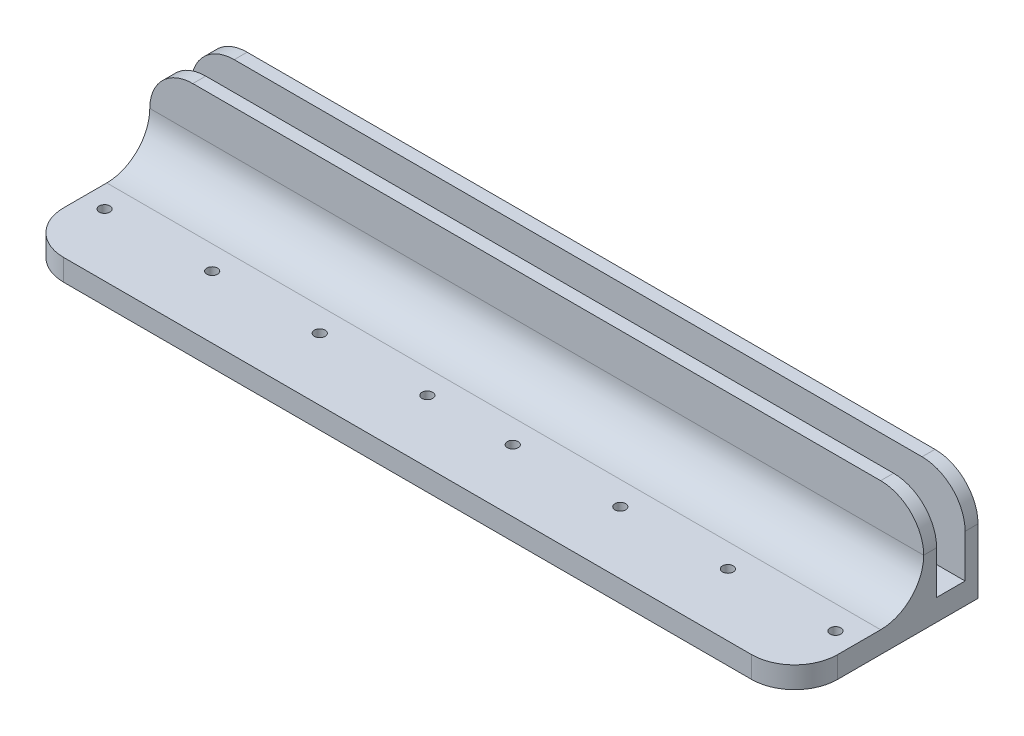
SolidWorks part; units mm, degrees
ref_plane "Front Plane" through (0, 0, 0) normal (0, 0, 1) x (1, 0, 0)
ref_plane "Top Plane" through (0, 0, 0) normal (0, 1, 0) x (1, 0, 0)
ref_plane "Right Plane" through (0, 0, 0) normal (1, 0, 0) x (0, 0, -1)
sketch "Sketch1" plane through (0, 0, 0) normal (0, 1, 0) x (1, 0, 0)
  line L1 (-80.9111, 25.148) -> (98.9289, 25.148)
  line L2 (-80.9111, 25.148) -> (-80.9111, -7.472)
  line L3 (-70.9111, -17.472) -> (88.9289, -17.472)
  line L4 (98.9289, 25.148) -> (98.9289, -7.472)
  line L5 (-80.9111, 25.148) -> (98.9289, 25.148)
  line L6 (-80.9111, 25.148) -> (-80.9111, 22.148)
  line L7 (-80.9111, 22.148) -> (98.9289, 22.148)
  line L8 (98.9289, 25.148) -> (98.9289, 22.148)
  line L9 (-80.9111, 22.148) -> (98.9289, 22.148)
  line L10 (-80.9111, 22.148) -> (-80.9111, 15.528)
  line L11 (-80.9111, 15.528) -> (98.9289, 15.528)
  line L12 (98.9289, 22.148) -> (98.9289, 15.528)
  line L13 (-80.9111, 15.528) -> (98.9289, 15.528)
  line L14 (-80.9111, 15.528) -> (-80.9111, 12.528)
  line L15 (-80.9111, 12.528) -> (98.9289, 12.528)
  line L16 (98.9289, 15.528) -> (98.9289, 12.528)
  circle A0 centre (-75.9111, -2.972) radius 1.25
  circle A1 centre (-50.9111, -2.972) radius 1.25
  circle A2 centre (-25.9111, -2.972) radius 1.25
  circle A3 centre (-0.9111, -2.972) radius 1.25
  circle A4 centre (18.9289, -2.972) radius 1.25
  circle A5 centre (43.9289, -2.972) radius 1.25
  circle A6 centre (68.9289, -2.972) radius 1.25
  circle A7 centre (93.9289, -2.972) radius 1.25
  arc A8 (98.9289, -7.472) -> (88.9289, -17.472) centre (88.9289, -7.472) cw
  arc A9 (-70.9111, -17.472) -> (-80.9111, -7.472) centre (-70.9111, -7.472) cw
  point P26 (0, 0)
  point P27 (0, 0)
  point P28 (0, 0)
  point P29 (-66.7579, 2.4725)
  point P30 (-45.4339, 1.8031)
  point P31 (-37.9753, 1.8987)
  point P32 (-28.8911, 0.3687)
  point P33 (19.3031, 0.0819)
  point P34 (0, 0)
  point P35 (8.2688, 1.0284)
  point P36 (0, 0)
  point P37 (0, 0)
  point P38 (-13.4243, 2.028)
  dimension "D6" = 2.5
  dimension "D7" = 2.5
  dimension "D8" = 2.5
  dimension "D9" = 2.5
  dimension "D10" = 2.5
  dimension "D11" = 2.5
  dimension "D12" = 2.5
  dimension "D13" = 2.5
  dimension "D23" = 10
  dimension "D1" = 6.62
  dimension "D2" = 3
  dimension "D3" = 3
  dimension "D4" = 30
  dimension "D5" = 15.5
  dimension "D14" = 25
  dimension "D15" = 25
  dimension "D16" = 5
  dimension "D17" = 25
  dimension "D18" = 25
  dimension "D19" = 19.84
  dimension "D20" = 25
  dimension "D21" = 25
  dimension "D22" = 5
extrude "Boss-Extrude1" add sketch "Sketch1" along normal blind 5 contours A9 L3 A8 L4 L15 L2 A7 A6 A5 A4 A3 A2 A1 A0 | L2 L15 L4 L11 | L2 L11 L4 L7 | L2 L7 L4 L1 region at (9.0089, 0, -23.648) region at (9.0089, 0, -18.838) region at (9.0089, 0, -14.028) region at (9.0089, 0, 2.3652)
extrude "Boss-Extrude2" add sketch "Sketch1<3>" along normal blind 20 from surface contours L2 L15 L4 L11 | L2 L7 L4 L1 region at (9.0089, 0, -23.648) region at (9.0089, 0, -14.028) starting at face at (9.0089, 5, 0.6224)
sketch "Sketch1<3>" plane through (0, 0, 0) normal (0, 1, 0) x (1, 0, 0) same geometry as "Sketch1"
fillet "Fillet1" radius 10 1 edges at (9.0089, 5, -12.528)
fillet "Fillet2" radius 10 4 edges at (-80.9111, 25, -23.648) (-80.9111, 25, -14.028) (98.9289, 25, -14.028) (98.9289, 25, -23.648)
